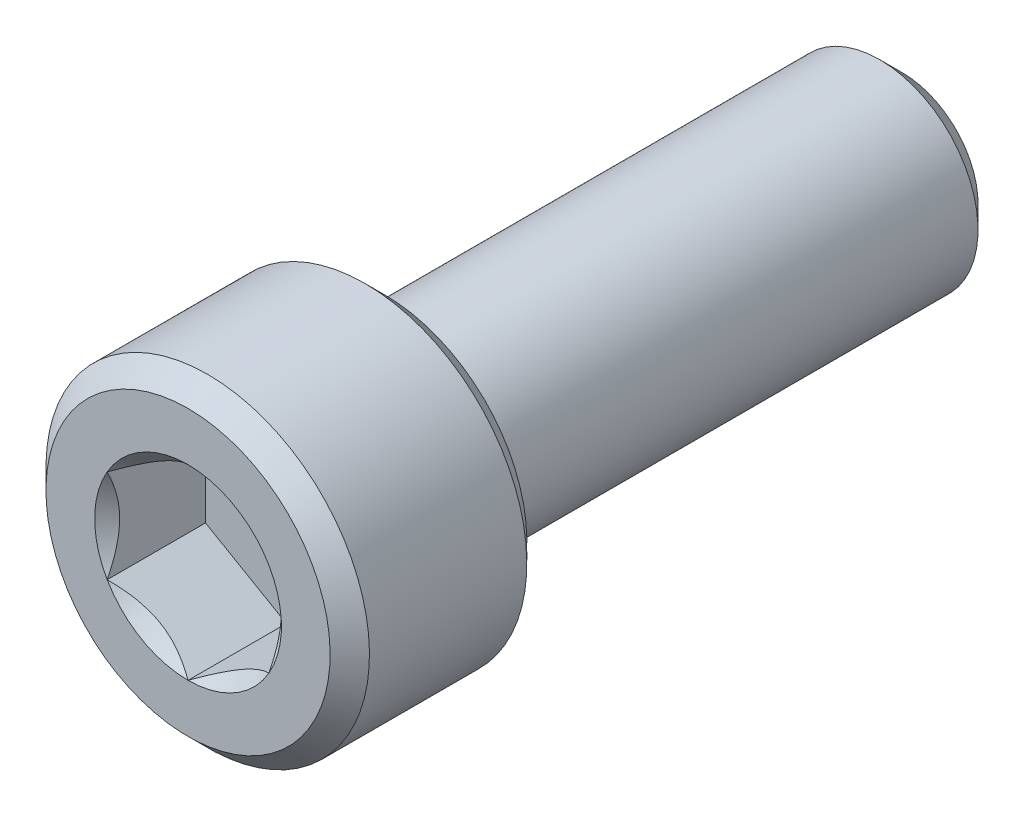
SolidWorks part; units mm, degrees
ref_plane "Front Plane" through (0, 0, 0) normal (0, 0, 1) x (1, 0, 0)
ref_plane "Top Plane" through (0, 0, 0) normal (0, 1, 0) x (1, 0, 0)
ref_plane "Right Plane" through (0, 0, 0) normal (1, 0, 0) x (0, 0, -1)
sketch "Sketch1" plane through (0, 0, 0) normal (1, 0, 0) x (0, 0, -1)
  line L0 (8.763, 0) -> (-8.763, 0) construction
  line L1 (-8.763, 0) -> (-8.763, 3.4861)
  line L2 (-8.763, 3.4861) -> (-8.2804, 3.9687)
  line L3 (-8.2804, 3.9687) -> (-4.4196, 3.9687)
  line L4 (-4.4196, 3.9687) -> (-3.937, 3.4861)
  line L5 (-3.937, 3.4861) -> (-3.937, 2.413)
  line L6 (-3.937, 2.413) -> (8.2074, 2.413)
  line L7 (8.2074, 2.413) -> (8.763, 1.8574)
  line L8 (8.763, 1.8574) -> (8.763, 0)
  line L9 (8.7134, 2.4989) -> (9.5071, 2.4989) construction
  line L10 (9.5071, 2.4989) -> (9.1103, 1.8115) construction
  line L11 (9.1103, 1.8115) -> (8.7134, 2.4989) construction
  line L12 (8.763, 2.413) -> (9.4575, 2.413) construction
  line L13 (9.1103, 2.4989) -> (9.1103, 2.413) construction
  line L14 (9.0607, 1.8974) -> (9.1599, 1.8974) construction
  line L15 (9.1103, 1.8974) -> (9.1103, 1.8115) construction
  line L16 (8.7382, 2.456) -> (9.4823, 2.456)
  line L17 (9.4823, 2.456) -> (9.1599, 1.8974)
  line L18 (9.1599, 1.8974) -> (9.0607, 1.8974)
  line L19 (9.0607, 1.8974) -> (8.7382, 2.456)
  line L20 (8.2074, -2.413) -> (6.7786, -2.413) construction
  point P3 (-8.0391, 3.9687)
  point P4 (0, 0)
  point P25 (9.1103, 2.456)
  point P26 (8.763, 2.413)
  point P28 (-4.6609, 3.9687)
  point P29 (-6.35, 3.9687)
  point P33 (6.7786, -2.413)
  dimension "Head Ht" = 4.826
  dimension "Screw Size" = 4.826
  dimension "Head Dia" = 7.9375
  dimension "D1" = 45
  dimension "D2" = 45
  dimension "D3" = 0.4826
  dimension "D4" = 0.4826
  dimension "Pitch" = 0.7937
  dimension "D5" = 0.0992
  dimension "D6" = 0.5556
  dimension "D7" = 1.4287
  dimension "Length" = 12.7
  dimension "D8" = 0.2413
  dimension "D9" = 0.2413
sketch "Sketch2" plane through (0, 0, 0) normal (0, 0, 1) x (1, 0, 0)
  line L1 (0, 2.2914) -> (-1.9844, 1.1457)
  line L2 (-1.9844, 1.1457) -> (-1.9844, -1.1457)
  line L3 (-1.9844, -1.1457) -> (0, -2.2914)
  line L4 (0, -2.2914) -> (1.9844, -1.1457)
  line L5 (1.9844, -1.1457) -> (1.9844, 1.1457)
  line L6 (1.9844, 1.1457) -> (0, 2.2914)
  line L8 (0, -3.9687) -> (0, 3.9687) construction
  circle A0 centre (0, 0) radius 1.9844 construction
  circle A1 centre (0, 0) radius 3.9687
  circle A2 centre (0, 0) radius 18.0975 construction
  point P1 (0, 3.9687)
  point P19 (0, 0)
  dimension "D1" = 7.9375
  dimension "D3" = 36.195
  dimension "Drive Size" = 3.9688
sketch "Sketch3" plane through (0, 0, 0) normal (1, 0, 0) x (0, 0, -1)
  line L0 (8.763, 0) -> (-8.763, 0) construction
  line L1 (-8.763, 0) -> (-8.763, 3.4861) construction
  line L2 (-8.763, 3.4861) -> (-8.2804, 3.9687) construction
  line L3 (-8.2804, 3.9687) -> (-4.4196, 3.9687) construction
  line L4 (-4.4196, 3.9687) -> (-3.937, 3.4861) construction
  line L5 (-3.937, 3.4861) -> (-3.937, 2.413) construction
  line L6 (-3.937, 2.413) -> (8.2074, 2.413) construction
  line L7 (8.2074, 2.413) -> (8.763, 1.8574) construction
  line L8 (8.763, 1.8574) -> (8.763, 0) construction
  line L9 (8.763, 0) -> (-8.763, 0)
  line L10 (-8.763, 0) -> (-8.763, 3.4861)
  line L11 (-8.763, 3.4861) -> (-8.2804, 3.9687)
  line L12 (-8.2804, 3.9687) -> (-4.4196, 3.9687)
  line L13 (-4.4196, 3.9687) -> (-3.937, 3.4861)
  line L14 (-3.937, 3.4861) -> (-3.937, 2.413)
  line L15 (-3.937, 2.413) -> (8.2074, 2.413)
  line L16 (8.2074, 2.413) -> (8.763, 1.8574)
  line L17 (8.763, 1.8574) -> (8.763, 0)
revolve "Revolve1" add sketch "Sketch3" angle 360 about L0
sketch "Sketch4" plane through (0, 0, 8.763) normal (0, 0, 1) x (1, 0, 0)
  line L0 (0, -2.2914) -> (1.9844, -1.1457) construction
  line L1 (1.9844, -1.1457) -> (1.9844, 1.1457) construction
  line L2 (1.9844, 1.1457) -> (0, 2.2914) construction
  line L3 (0, 2.2914) -> (-1.9844, 1.1457) construction
  line L4 (-1.9844, 1.1457) -> (-1.9844, -1.1457) construction
  line L5 (-1.9844, -1.1457) -> (0, -2.2914) construction
  line L6 (0, -2.2914) -> (1.9844, -1.1457)
  line L7 (1.9844, -1.1457) -> (1.9844, 1.1457)
  line L8 (1.9844, 1.1457) -> (0, 2.2914)
  line L9 (0, 2.2914) -> (-1.9844, 1.1457)
  line L10 (-1.9844, 1.1457) -> (-1.9844, -1.1457)
  line L11 (-1.9844, -1.1457) -> (0, -2.2914)
extrude "Cut-Extrude1" cut sketch "Sketch4" against normal blind 2.413
sketch "Sketch5" plane through (0, 0, 8.763) normal (0, 0, 1) x (1, 0, 0)
  circle A0 centre (0, 0) radius 2.2914
extrude "Cut-Extrude3" cut sketch "Sketch5" against normal through all draft 45
ref_axis "Center Axis1" through (0, 0, 3.937) along (0, 0, -1)
split "Split1" [suppressed] bodies to split 107
sketch "Sketch6" [suppressed] plane through (0, 0, -8.763) normal (0, 0, -1) x (-1, 0, 0)
  circle A0 centre (0, 0) radius 2.413 construction
  circle A1 centre (0, 0) radius 2.413
curve "Helix/Spiral1" [suppressed] pitch 0.7937 height 13.4937 turns 17
sketch "Sketch7" [suppressed] plane through (0, 0, 0) normal (1, 0, 0) x (0, 0, -1)
  line L0 (8.7382, 2.456) -> (9.4823, 2.456) construction
  line L1 (9.4823, 2.456) -> (9.1599, 1.8974) construction
  line L2 (9.1599, 1.8974) -> (9.0607, 1.8974) construction
  line L3 (9.0607, 1.8974) -> (8.7382, 2.456) construction
  line L4 (8.7382, 2.456) -> (9.4823, 2.456)
  line L5 (9.4823, 2.456) -> (9.1599, 1.8974)
  line L6 (9.1599, 1.8974) -> (9.0607, 1.8974)
  line L7 (9.0607, 1.8974) -> (8.7382, 2.456)
sweep "Cut-Sweep1" [suppressed] cut profiles "Sketch7" path "Helix/Spiral1"
sketch "Sketch8" [suppressed] plane through (0, 0, 3.937) normal (0, 0, -1) x (-1, 0, 0)
  circle A0 centre (0, 0) radius 2.413
  point P3 (0, 2.413)
extrude "Boss-Extrude1" [suppressed] add sketch "Sketch8" along normal blind 2.54 draft 80
equation "\"D3@Sketch1\"=\"Head Ht@Sketch1\"/10"
equation "\"D4@Sketch1\"=\"Head Ht@Sketch1\"/10"
equation "\"D5@Sketch1\"=\"Pitch@Sketch1\"/8"
equation "\"D6@Sketch1\"=\"Pitch@Sketch1\"*.7"
equation "\"D7@Sketch1\"=\"Pitch@Sketch1\"*2.5-\"D6@Sketch1\""
equation "\"D1@Cut-Extrude1\"=\"Head Ht@Sketch1\"/2"
equation "\"D4@Helix/Spiral1\"=\"Pitch@Sketch1\""
equation "\"D3@Helix/Spiral1\"=\"Length@Sketch1\"+\"D4@Helix/Spiral1\""
equation "\"D8@Sketch1\"=\"D4@Sketch1\"/2"
equation "\"D9@Sketch1\"=\"D3@Sketch1\"/2"
